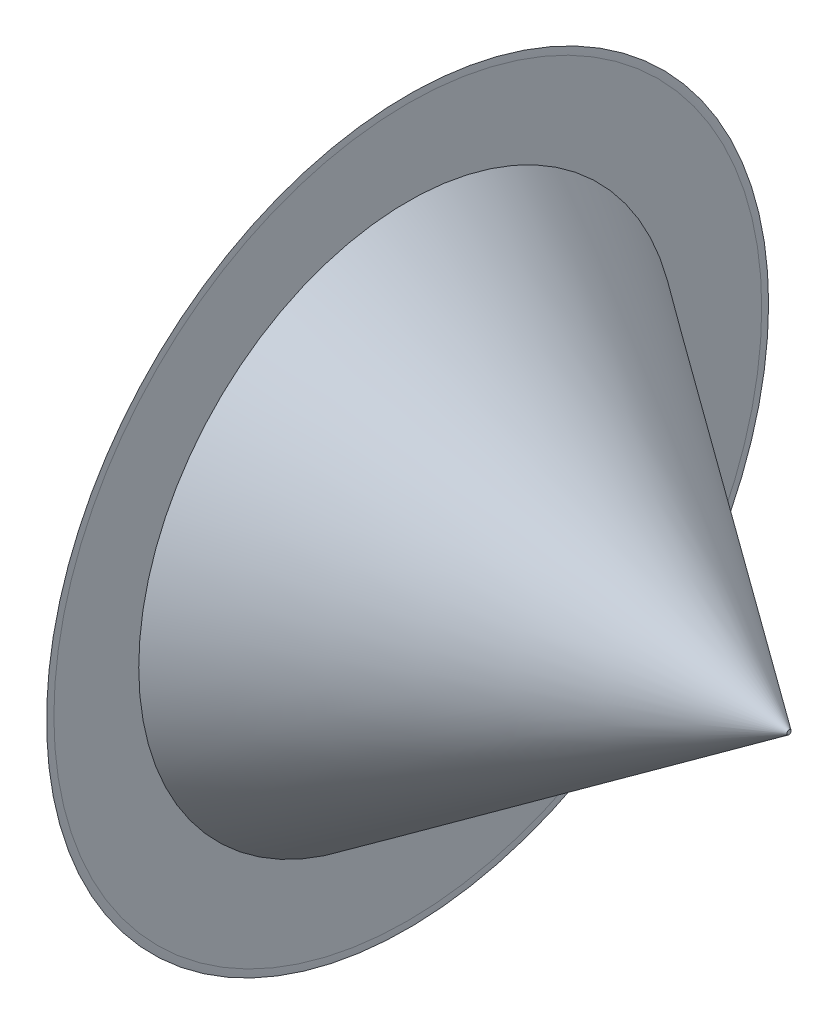
SolidWorks part; units mm, degrees
ref_plane "Front Plane" through (0, 0, 0) normal (0, 0, 1) x (1, 0, 0)
ref_plane "Top Plane" through (0, 0, 0) normal (0, 1, 0) x (1, 0, 0)
ref_plane "Right Plane" through (0, 0, 0) normal (1, 0, 0) x (0, 0, -1)
sketch "Sketch1" plane through (0, 0, 0) normal (1, 0, 0) x (0, 0, -1)
  circle A0 centre (0, 0) radius 16.1
extrude "Boss-Extrude1" add sketch "Sketch1" along normal blind 0.01
fillet "Fillet1" radius 5 1 edges at (0.01, 0, -16.1)
sketch "Sketch2" plane through (0.01, 0, 0) normal (1, 0, 0) x (0, 0, -1)
  circle A0 centre (0, 0) radius 12
extrude "Boss-Extrude2" add sketch "Sketch2" along normal blind 17
chamfer "Chamfer1" distance 17 angle 35 1 edges at (17.01, 0, -12) first distance on face at (17.01, 0, -12)
